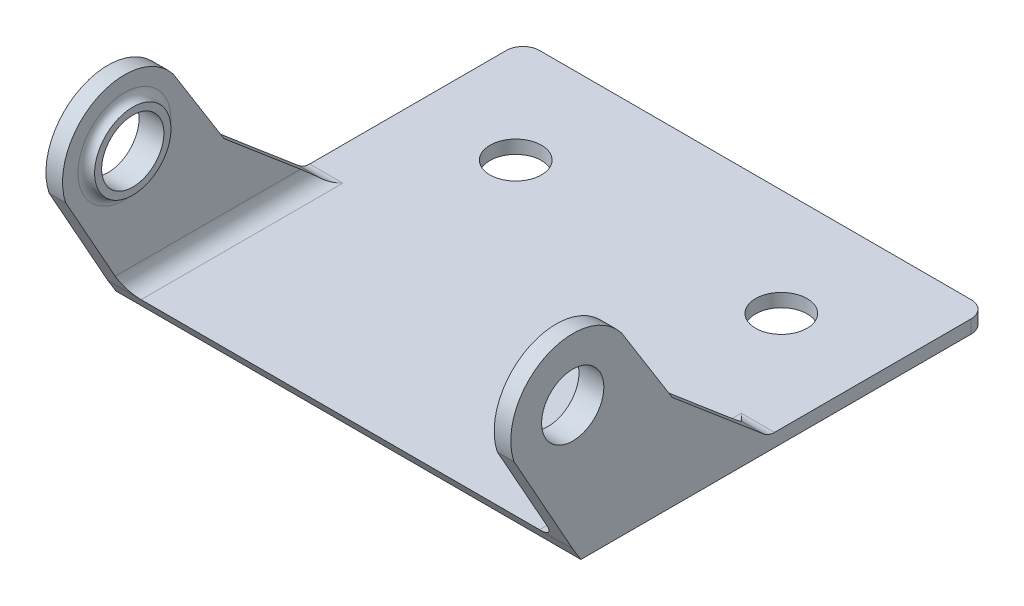
SolidWorks part; units mm, degrees
note: The reader was unsure of these and kept them because the rebuilt part matched: shared geometry of "Sketch2<3>", "Sketch2<4>".
material "Galvanized Steel"
ref_plane "Front Plane" through (0, 0, 0) normal (0, 0, 1) x (1, 0, 0)
ref_plane "Top Plane" through (0, 0, 0) normal (0, 1, 0) x (1, 0, 0)
ref_plane "Right Plane" through (0, 0, 0) normal (1, 0, 0) x (0, 0, -1)
sketch "Sketch1" plane through (0, 0, 0) normal (0, 1, 0) x (1, 0, 0)
  line L1 (-20.32, -47.1551) -> (20.32, -47.1551)
  line L3 (-38.1, -47.1551) -> (38.1, -47.1551)
  line L4 (-38.1, -47.1551) -> (-38.1, 16.3449)
  line L5 (-38.1, 16.3449) -> (38.1, 16.3449)
  line L6 (38.1, 16.3449) -> (38.1, -47.1551)
  circle A0 centre (-20.32, 0) radius 2.7051
  circle A1 centre (20.32, 0) radius 2.7051
  point P10 (0, -47.1551)
extrude "Boss-Extrude1" add sketch "Sketch1" along normal blind 2.032 contours L6 L5 L4 L3 L1 A1 A0
sketch "Sketch2" plane through (38.1, 0, 0) normal (1, 0, 0) x (0, 0, -1)
  line L0 (-31.9306, 14.4926) -> (-39.7153, 26.9533)
  line L2 (-47.1551, 2.032) -> (-47.1551, 0)
  line L3 (16.3449, 2.032) -> (-47.1551, 2.032) construction
  line L4 (-47.1551, 0) -> (-45.9096, 0)
  line L5 (-47.1551, 2.032) -> (-56.1517, 18.1013)
  line L6 (-47.1551, 2.032) -> (-45.9096, 0)
  line L7 (16.3449, 0) -> (-47.1551, 0) construction
  line L8 (-47.1551, 2.032) -> (-24.1459, 2.032)
  line L9 (-17.2167, 2.032) -> (-31.9306, 14.4926)
  circle A0 centre (-47.1551, 21.082) radius 4.7625
  arc A1 (-38.6159, 25.1935) -> (-54.3988, 14.9704) centre (-47.1551, 21.082) ccw
  line M5 (16.3449, 2.032) -> (-47.1551, 2.032)
extrude "Cut-Extrude1" cut sketch "Sketch2" against normal through all contours L2 L4 L6
extrude "Boss-Extrude2" add sketch "Sketch2<3>" against normal blind 2.54 from offset 2.54 contours L0 A1 L5 L9 A0 M5 offset against normal yes
sketch "Sketch2<3>" plane through (38.1, 0, 0) normal (1, 0, 0) x (0, 0, -1) same geometry as "Sketch2"
extrude "Boss-Extrude3" add sketch "Sketch2<4>" against normal blind 2.54 from offset 71.12 contours L0 A1 L5 L9 A0 M5 offset against normal yes
sketch "Sketch2<4>" plane through (38.1, 0, 0) normal (1, 0, 0) x (0, 0, -1) same geometry as "Sketch2"
sketch "Sketch3" plane through (0, 2.032, 0) normal (0, 1, 0) x (1, 0, 0)
  line L0 (-35.56, -47.1551) -> (-38.1, -47.1551)
  line L1 (-38.1, -47.1551) -> (-38.1, 16.3449)
  line L2 (-38.1, 16.3449) -> (-35.56, 16.3449)
  line L3 (-38.1, 16.3449) -> (38.1, 16.3449) construction
  line L4 (-35.56, 16.3449) -> (-35.56, -47.1551)
  line L5 (35.56, -47.1551) -> (38.1, -47.1551)
  line L6 (38.1, -47.1551) -> (38.1, 16.3449)
  line L7 (38.1, 16.3449) -> (36.83, 16.3449)
  line L8 (36.83, 16.3449) -> (35.56, 16.3449)
  line L9 (35.56, 16.3449) -> (35.56, -47.1551)
extrude "Cut-Extrude2" cut sketch "Sketch3" against normal through all
fillet "Fillet1" radius 2.54 4 edges at (34.29, 2.032, 17.2167) (33.02, 2.032, 32.1859) (-34.29, 2.032, 17.2167) (-33.02, 2.032, 32.1859)
fillet "Fillet2" radius 2.54 1 edges at (-35.56, 1.016, -16.3449)
fillet "Fillet3" radius 2.54 1 edges at (35.56, 1.016, -16.3449)
sketch "Sketch4" plane through (-33.02, 0, 0) normal (1, 0, 0) x (0, 0, -1)
  circle A0 centre (-47.1551, 21.082) radius 4.7625
  circle A1 centre (-47.1551, 21.082) radius 5.842
  dimension "D1" = 9.525
  dimension "D2" = 11.684
extrude "Boss-Extrude4" add sketch "Sketch4" along normal blind 1.27
fillet "Fillet4" radius 1.27 1 edges at (-33.02, 21.082, 41.3131)
sketch "Sketch5" plane through (33.02, 0, 0) normal (-1, 0, 0) x (0, 0, 1)
  circle A0 centre (47.1551, 21.082) radius 4.7625
  circle A1 centre (47.1551, 21.082) radius 5.842
  dimension "D1" = 9.525
  dimension "D2" = 11.684
extrude "Boss-Extrude5" add sketch "Sketch5" along normal blind 1.27
fillet "Fillet5" radius 1.27 1 edges at (33.02, 21.082, 41.3131)
sketch "Sketch6" plane through (0, 2.032, 0) normal (0, 1, 0) x (1, 0, 0)
  circle A0 centre (-20.32, 0) radius 3.937
  circle A1 centre (20.32, 0) radius 3.937
  dimension "D1" = 7.874
  dimension "D2" = 7.874
extrude "Cut-Extrude3" cut sketch "Sketch6" against normal blind 2.54
